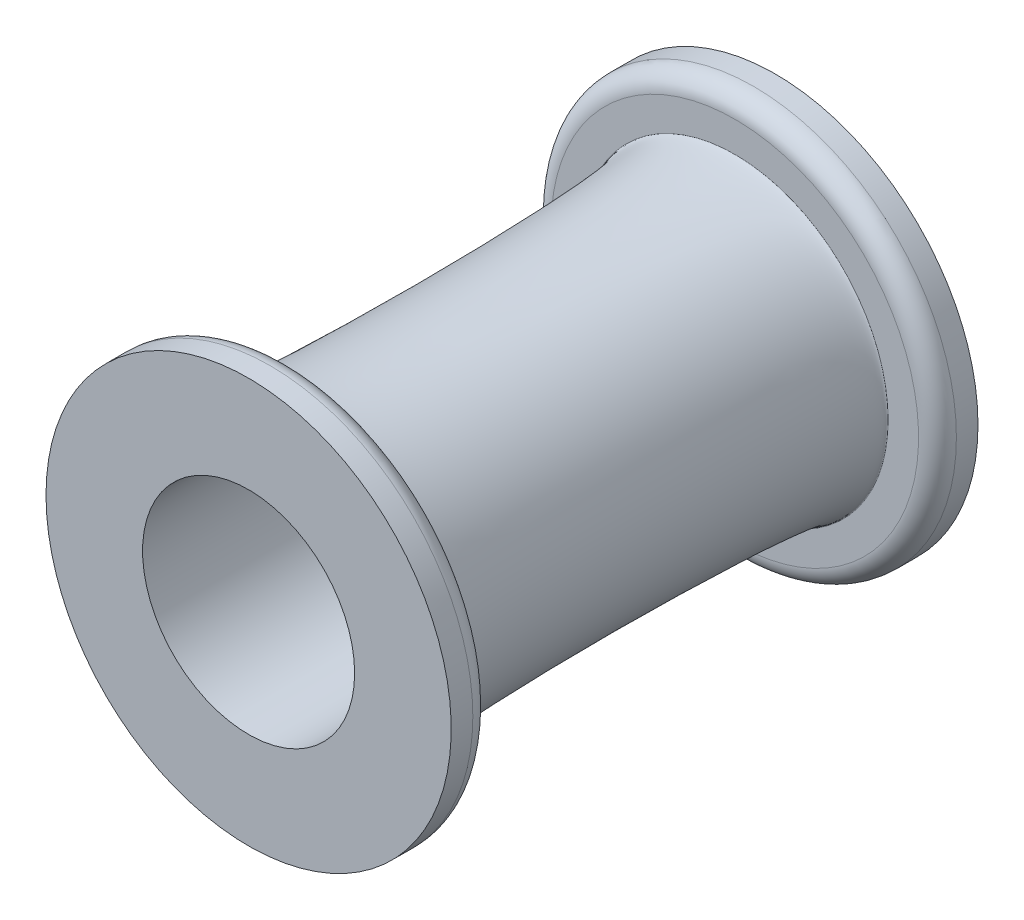
SolidWorks part; units mm, degrees
ref_plane "Front Plane" through (0, 0, 0) normal (0, 0, 1) x (1, 0, 0)
ref_plane "Top Plane" through (0, 0, 0) normal (0, 1, 0) x (1, 0, 0)
ref_plane "Right Plane" through (0, 0, 0) normal (1, 0, 0) x (0, 0, -1)
sketch "Sketch1" plane through (0, 0, 0) normal (0, 0, 1) x (1, 0, 0)
  circle A0 centre (0, 0) radius 9.9695
  circle A1 centre (0, 0) radius 14.4145
  dimension "D1" = 19.939
  dimension "D2" = 28.829
extrude "Boss-Extrude1" add sketch "Sketch1" along normal blind 41.91
ref_plane "Plane1" through (0, 0, 20.955) normal (0, 0, 1) x (1, 0, 0)
sketch "Sketch2" plane through (0, 0, 41.91) normal (0, 0, 1) x (1, 0, 0)
  circle A0 centre (0, 0) radius 9.9695 construction
  circle A1 centre (0, 0) radius 9.9695
  circle A2 centre (0, 0) radius 19.05
  dimension "D1" = 38.1
extrude "Boss-Extrude2" add sketch "Sketch2" along normal blind 3.81
mirror "Mirror1" about plane through (0, 0, 20.955) normal (0, 0, 1) of "Boss-Extrude2"
fillet "Fillet1" radius 1.778 2 edges at (19.05, 0, 41.91) (19.05, 0, 0)
ref_axis "Axis1" through (0, 0, 45.72) along (0, 0, -1)
sketch "Sketch3" plane through (0, 0, 0) normal (0, 1, 0) x (1, 0, 0)
  line L0 (-14.4145, 0) -> (-14.4145, -41.91) construction
  ellipse E0 centre (-14.4145, -20.955) end of major axis (-14.4145, -41.91) minor radius 1.1359
revolve "Cut-Revolve1" cut sketch "Sketch3" angle 360 about axis through (0, 0, 45.72) along (0, 0, -1)
